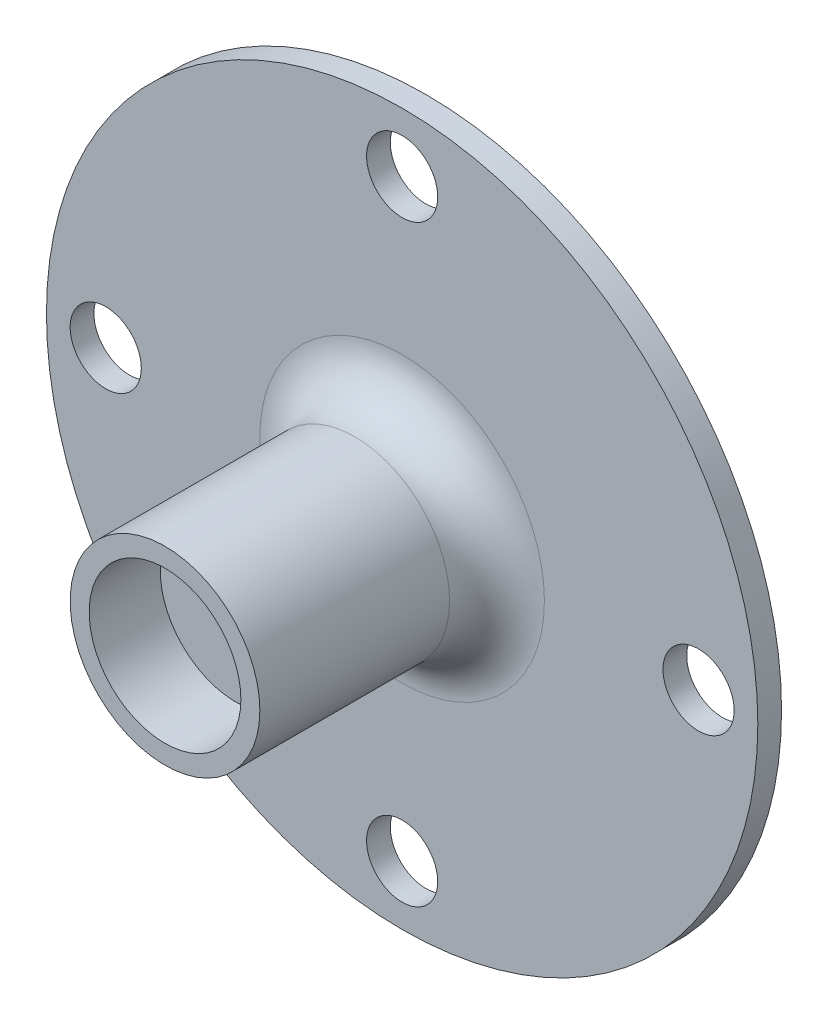
SolidWorks part; units mm, degrees
ref_plane "Front Plane" through (0, 0, 0) normal (0, 0, 1) x (1, 0, 0)
ref_plane "Top Plane" through (0, 0, 0) normal (0, 1, 0) x (1, 0, 0)
ref_plane "Right Plane" through (0, 0, 0) normal (1, 0, 0) x (0, 0, -1)
sketch "Sketch1" plane through (0, 0, 0) normal (0, 0, 1) x (1, 0, 0)
  circle A0 centre (0, 0) radius 12.5 construction
  circle A1 centre (0, 12.5) radius 1.5
  circle A2 centre (12.5, 0) radius 1.5
  circle A3 centre (0, -12.5) radius 1.5
  circle A4 centre (-12.5, 0) radius 1.5
  circle A5 centre (0, 0) radius 15
  circle A6 centre (0, 0) radius 4
  circle A7 centre (0, 0) radius 3.2
  point P14 (0, 0)
  dimension "D1" = 25
  dimension "D2" = 3
  dimension "D4" = 30
  dimension "D5" = 8
  dimension "D6" = 6.4
  dimension "D3" = 4
extrude "Boss-Extrude1" add sketch "Sketch1" along normal blind 1 contours A5 A6 A1 A2 A3 A4 region at (-14.5757, 0, 0)
extrude "Boss-Extrude2" add sketch "Sketch1<4>" along normal blind 11 contours A6 A7 region at (-3.8869, 0, 0)
sketch "Sketch1<4>" plane through (0, 0, 0) normal (0, 0, 1) x (1, 0, 0) same geometry as "Sketch1"
extrude "Boss-Extrude3" add sketch "Sketch1<5>" along normal offset from surface (8 mm away) 3 contours A7 region at (0, 0, 0) up to face at (3.2, 0, 11)
sketch "Sketch1<5>" plane through (0, 0, 0) normal (0, 0, 1) x (1, 0, 0) same geometry as "Sketch1"
fillet "Fillet1" radius 2 1 edges at (4, 0, 1)
